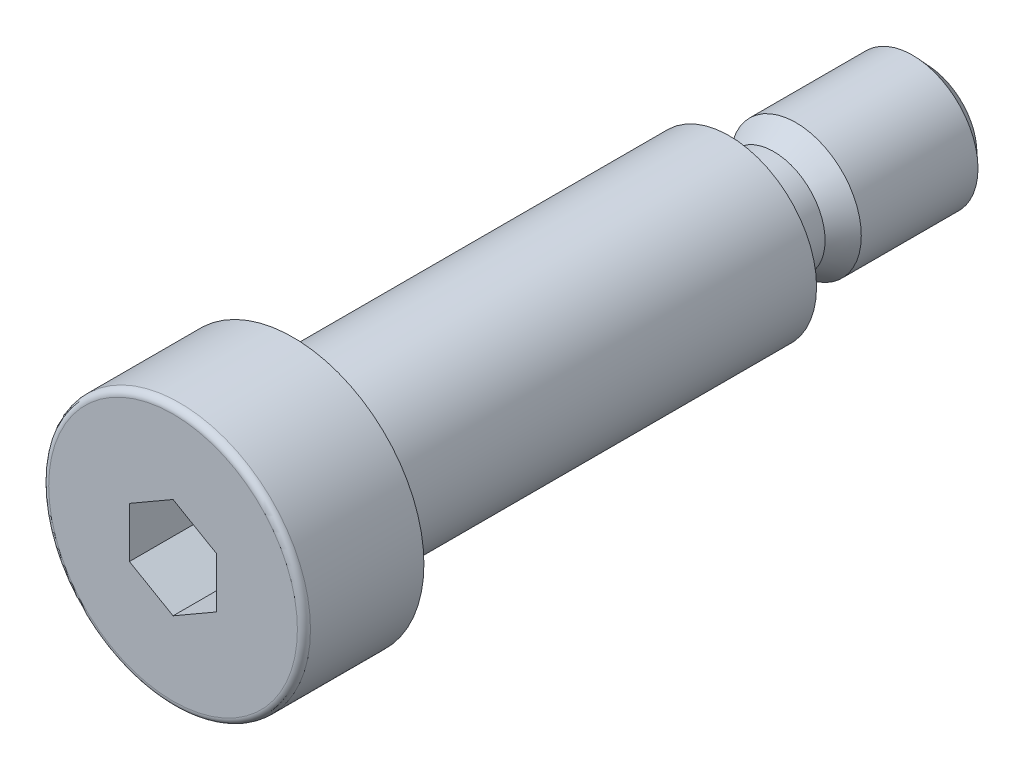
SolidWorks part; units mm, degrees
material "1.0545 (S355N)"
ref_plane "Płaszczyzna przednia" through (0, 0, 0) normal (0, 0, 1) x (1, 0, 0)
ref_plane "Płaszczyzna górna" through (0, 0, 0) normal (0, 1, 0) x (1, 0, 0)
ref_plane "Płaszczyzna prawa" through (0, 0, 0) normal (1, 0, 0) x (0, 0, -1)
sketch "Szkic1" plane through (0, 0, 0) normal (0, 1, 0) x (1, 0, 0)
  line L0 (6, 26.1) -> (4.7, 24.08)
  line L1 (12, -31) -> (-12, -31)
  line L2 (12, -31) -> (12, -20)
  line L3 (12, -20) -> (-12, -20)
  line L4 (-12, -31) -> (-12, -20)
  line L5 (8, -20) -> (-8, -20)
  line L6 (8, -20) -> (8, 20)
  line L7 (8, 20) -> (-8, 20)
  line L8 (-8, -20) -> (-8, 20)
  line L9 (-4.7, 20) -> (4.7, 20)
  line L10 (-4.7, 20) -> (-4.7, 24.08)
  line L11 (-4.7, 24.08) -> (4.7, 24.08)
  line L12 (4.7, 20) -> (4.7, 24.08)
  line L13 (6, 26.1) -> (6, 36.8)
  line L14 (6, 36.8) -> (4.7, 38)
  line L15 (4.7, 38) -> (-4.7, 38)
  line L16 (-4.7, 38) -> (-6, 36.8)
  line L17 (-6, 36.8) -> (-6, 26.1)
  line L18 (-6, 26.1) -> (-4.7, 24.08)
  line L19 (6, 26.1) -> (-6, 26.1) construction
  line L20 (6, 36.8) -> (-6, 36.8) construction
  line L21 (0, -19.9356) -> (0, 25.6583) construction
  line L22 (0, -31) -> (0, 38)
  point P4 (0, -20)
  point P14 (0, -20)
  point P15 (0, 20)
  point P16 (0, 20)
  point P17 (-8, 0)
  point P23 (0, 26.1)
  point P25 (0, 38)
  point P26 (0, 24.08)
  point P27 (0, 36.8)
  dimension "D1" = 24
  dimension "D2" = 11
  dimension "D3" = 16
  dimension "l1" = 40
  dimension "D5" = 9.4
  dimension "D6" = 18
  dimension "D7" = 12
  dimension "D8" = 9.4
  dimension "D9" = 1.2
  dimension "D10" = 2.02
  dimension "D11" = 10.7
revolve "Obrót1" add sketch "Szkic1" angle 360 about L22 region at (-2.35, 0, -22.04) region at (-2.934, 0, -31.0785) region at (-4, 0, 0) region at (-6, 0, 25.5)
sketch "Szkic2" plane through (0, 0, 31) normal (0, 0, 1) x (1, 0, 0)
  line L1 (4, 2.3094) -> (0, 4.6188)
  line L2 (0, 4.6188) -> (-4, 2.3094)
  line L3 (-4, 2.3094) -> (-4, -2.3094)
  line L4 (-4, -2.3094) -> (0, -4.6188)
  line L5 (0, -4.6188) -> (4, -2.3094)
  line L6 (4, -2.3094) -> (4, 2.3094)
  circle A0 centre (0, 0) radius 4 construction
  dimension "D1" = 8
extrude "Wytnij-wyciągnięcie1" cut sketch "Szkic2" against normal blind 6.6
fillet "Zaokrąglenie1" radius 0.6 1 edges at (12, 0, 31)
